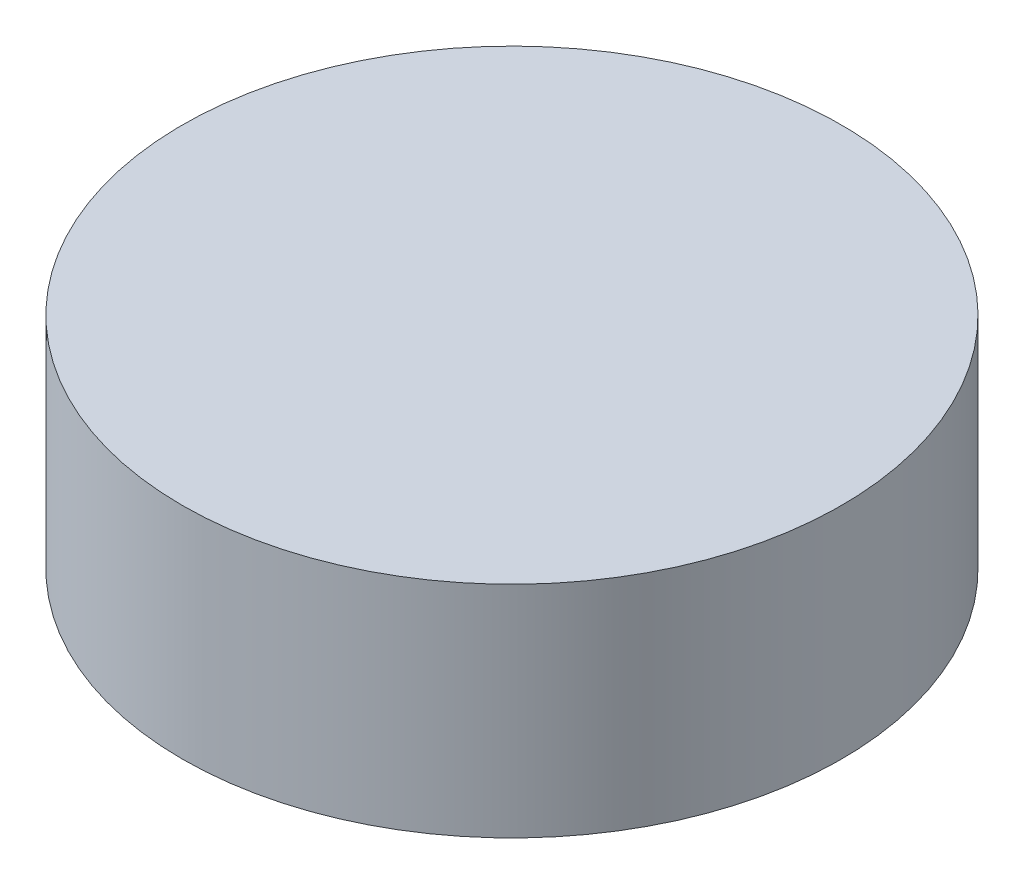
SolidWorks part; units mm, degrees
ref_plane "Front Plane" through (0, 0, 0) normal (0, 0, 1) x (1, 0, 0)
ref_plane "Top Plane" through (0, 0, 0) normal (0, 1, 0) x (1, 0, 0)
ref_plane "Right Plane" through (0, 0, 0) normal (1, 0, 0) x (0, 0, -1)
sketch "Sketch1" plane through (0, 0, 0) normal (0, 1, 0) x (1, 0, 0)
  circle A0 centre (0, 0) radius 30
  dimension "D1" = 60
extrude "Boss-Extrude1" add sketch "Sketch1" along normal mid plane 20
